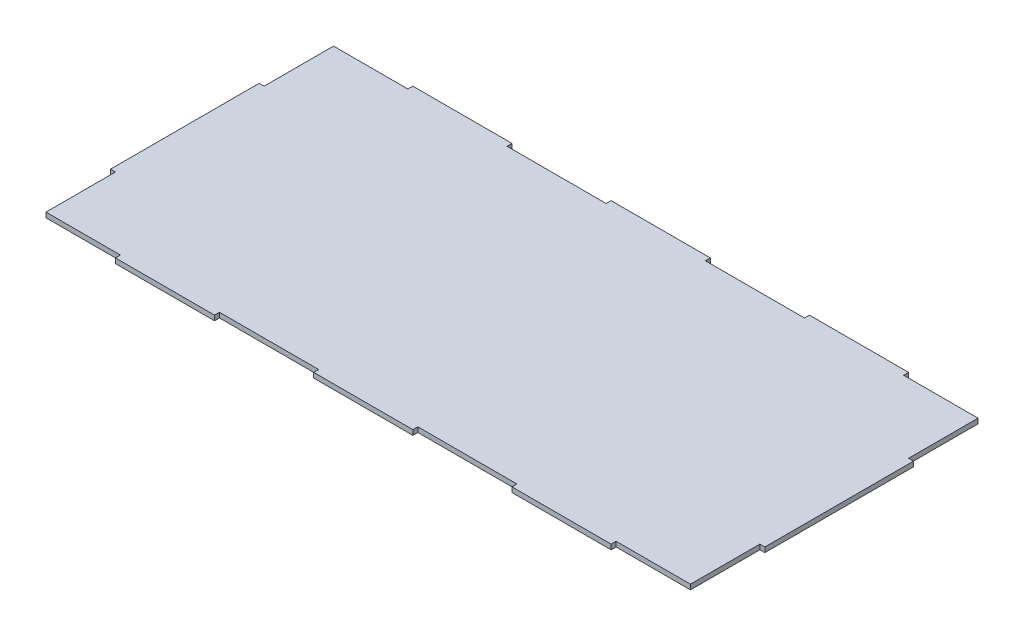
SolidWorks part; units mm, degrees
ref_plane "Ebene vorne" through (0, 0, 0) normal (0, 0, 1) x (1, 0, 0)
ref_plane "Ebene oben" through (0, 0, 0) normal (0, 1, 0) x (1, 0, 0)
ref_plane "Ebene rechts" through (0, 0, 0) normal (1, 0, 0) x (0, 0, -1)
sketch "Skizze1" plane through (0, 0, 0) normal (0, 1, 0) x (1, 0, 0)
  line L1 (-325, -145) -> (325, -145)
  line L2 (-325, -145) -> (-325, 145)
  line L3 (-325, 145) -> (325, 145)
  line L4 (325, -145) -> (325, 145)
  line L5 (-325, -145) -> (325, 145) construction
  line L6 (-325, 145) -> (325, -145) construction
  point P0 (0, 0)
  dimension "D1" = 650
  dimension "D2" = 290
extrude "Aufsatz-Linear austragen1" add sketch "Skizze1" along normal blind 5
sketch "Skizze2" plane through (0, 5, 0) normal (0, 1, 0) x (1, 0, 0)
  line L0 (-325, 0) -> (0, 0) construction
  line L1 (-325, 145) -> (-325, -145) construction
  line L2 (0, 0) -> (0, 145) construction
  line L3 (325, 145) -> (-325, 145) construction
  line L4 (50, 145) -> (-50, 145)
  line L5 (-50, 145) -> (-50, 150)
  line L6 (-50, 150) -> (50, 150)
  line L7 (50, 145) -> (50, 150)
  line L8 (-250, 145) -> (-150, 145)
  line L9 (-250, 145) -> (-250, 150)
  line L10 (-250, 150) -> (-150, 150)
  line L11 (-150, 145) -> (-150, 150)
  line L12 (150, 145) -> (150, 150)
  line L13 (250, 150) -> (150, 150)
  line L14 (250, 145) -> (250, 150)
  line L15 (250, 145) -> (150, 145)
  line L16 (250, -145) -> (150, -145)
  line L17 (250, -145) -> (250, -150)
  line L18 (250, -150) -> (150, -150)
  line L19 (150, -145) -> (150, -150)
  line L20 (-150, -145) -> (-150, -150)
  line L21 (-250, -150) -> (-150, -150)
  line L22 (-250, -145) -> (-250, -150)
  line L23 (-250, -145) -> (-150, -145)
  line L24 (50, -145) -> (50, -150)
  line L25 (-50, -150) -> (50, -150)
  line L26 (-50, -145) -> (-50, -150)
  line L27 (50, -145) -> (-50, -145)
  line L28 (-325, -75) -> (-325, 75)
  line L29 (-325, 75) -> (-330, 75)
  line L30 (-330, 75) -> (-330, -75)
  line L31 (-325, -75) -> (-330, -75)
  line L32 (325, -75) -> (330, -75)
  line L33 (330, 75) -> (330, -75)
  line L34 (325, 75) -> (330, 75)
  line L35 (325, -75) -> (325, 75)
  point P16 (0, 150)
  point P33 (0, -150)
  point P38 (-330, 0)
  point P43 (330, 0)
  dimension "D1" = 5
  dimension "D2" = 100
  dimension "D3" = 100
  dimension "D4" = 150
  dimension "D5" = 5
extrude "Aufsatz-Linear austragen3" add sketch "Skizze2" against normal up to surface (5 mm away) up to face at (0, 0, 0)
